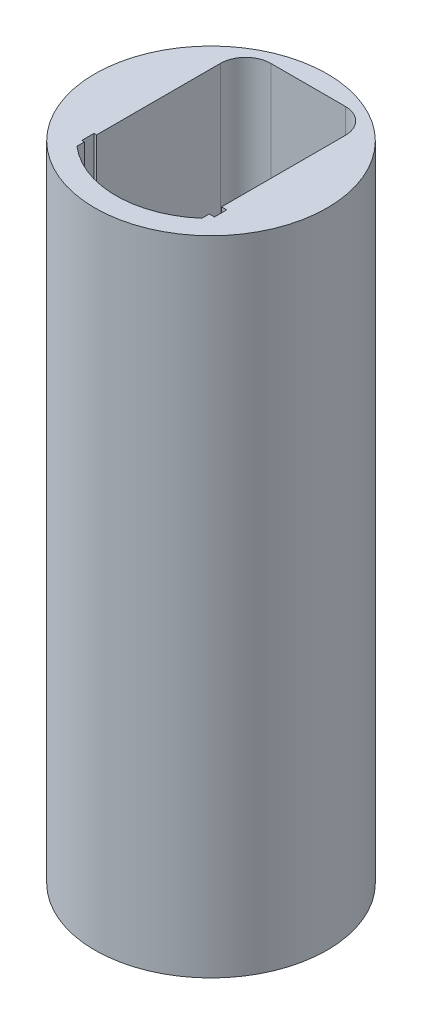
SolidWorks part; units mm, degrees
ref_plane "Front Plane" through (0, 0, 0) normal (0, 0, 1) x (1, 0, 0)
ref_plane "Top Plane" through (0, 0, 0) normal (0, 1, 0) x (1, 0, 0)
ref_plane "Right Plane" through (0, 0, 0) normal (1, 0, 0) x (0, 0, -1)
sketch "Sketch1" plane through (0, 0, 0) normal (0, 1, 0) x (1, 0, 0)
  line L0 (8.375, -6.9643) -> (9.075, -6.9643)
  line L1 (-8.725, -6.9643) -> (-8.375, -6.9643)
  line L2 (-8.725, -6.9643) -> (-8.725, -8.6143)
  line L3 (-8.725, -8.6143) -> (-8.375, -8.6143)
  line L4 (9.075, -6.9643) -> (9.075, -8.6143)
  line L6 (-8.375, -6.9643) -> (-8.375, -6.2043)
  line L12 (8.375, -6.9643) -> (8.375, -6.2043)
  line L14 (-8.375, -6.2043) -> (-8.375, 9.6457)
  line L16 (8.375, -6.2043) -> (8.375, 9.6457)
  line L19 (-5, 13.0207) -> (5, 13.0207)
  line L22 (-8.375, -8.6143) -> (-8.375, -9.6109)
  line L24 (8.375, -8.6143) -> (8.375, -9.6109)
  line L25 (8.375, -8.6143) -> (9.075, -8.6143)
  circle A0 centre (0, 0) radius 15.5912
  arc A1 (-5, 13.0207) -> (-8.375, 9.6457) centre (-5, 9.6457) ccw
  arc A2 (8.375, 9.6457) -> (5, 13.0207) centre (5, 9.6457) ccw
  arc A4 (-8.375, -9.6109) -> (8.375, -9.6109) centre (0, 0) ccw
  dimension "D5" = 16.75
  dimension "D6" = 0.76
  dimension "D1" = 17.8
  dimension "D2" = 1.65
  dimension "D3" = 15.85
  dimension "D4" = 10
  dimension "D8" = 0.35
  dimension "D9" = 0.7
extrude "Boss-Extrude1" add sketch "Sketch1" along normal blind 71
sketch "Sketch2" plane through (0, 0, 0) normal (0, -1, 0) x (1, 0, 0)
  line L1 (-8.725, 8.6143) -> (9.075, 8.6143)
  line L2 (-8.725, 8.6143) -> (-8.725, 6.9643)
  line L3 (-8.725, 6.9643) -> (9.075, 6.9643)
  line L4 (9.075, 8.6143) -> (9.075, 6.9643)
  circle A0 centre (0, 0) radius 15.5912
extrude "Boss-Extrude2" add sketch "Sketch2" along normal blind 1.25
sketch "Sketch3" plane through (0, -1.25, 0) normal (0, -1, 0) x (1, 0, 0)
  circle A0 centre (0, 0) radius 15.5912
extrude "Boss-Extrude3" add sketch "Sketch3" along normal blind 4
sketch "Sketch16" plane through (0, 0, 0) normal (0, 1, 0) x (1, 0, 0)
  line L0 (-3, -9.9011) -> (0, -9.9011)
  line L1 (0, -9.9011) -> (3, -9.9011)
  line L2 (3, -9.9011) -> (6, -9.9011)
  line L3 (-3, -9.9011) -> (-6, -9.9011)
  line L5 (-1.4599, -11.5773) -> (1.5401, -11.5773)
  line L6 (1.5401, -11.5773) -> (4.5401, -11.5773)
  circle A0 centre (0, -9.9011) radius 0.75
  circle A1 centre (3, -9.9011) radius 0.75
  circle A2 centre (-3, -9.9011) radius 0.75
  circle A3 centre (-6, -9.9011) radius 0.75
  circle A4 centre (6, -9.9011) radius 0.75
  circle A6 centre (1.5401, -11.5773) radius 0.75
  arc A9 (5.2892, -11.5989) -> (4.0065, -12.102) centre (4.5396, -11.5745) ccw
  arc A10 (-3.9429, -12.1229) -> (-5.2052, -11.6369) centre (-4.4576, -11.5773) ccw
  circle A11 centre (-1.4576, -11.5771) radius 0.75
  arc A12 (4.0065, -12.102) -> (5.2892, -11.5989) centre (0, 0) ccw
  arc A13 (-5.2052, -11.6369) -> (-3.9429, -12.1229) centre (0, 0) ccw
  dimension "D1" = 1.5
  dimension "D2" = 3
  dimension "D3" = 1.5
  dimension "D4" = 3
extrude "Cut-Extrude4" cut sketch "Sketch16" against normal blind 11.5 contours A4 | L2 A1 L1 | L1 A1 L2 | L1 A0 L0 | L0 A0 L1 | L0 A2 L3 | L3 A2 L0 | A3 | A6 | A0 | A9 A12 | A11 | A10 A13 region at (-3, 0, 9.5828) region at (-3, 0, 10.2194) region at (6, 0, 9.1723) region at (3, 0, 9.5828) region at (3, 0, 10.2194) region at (0, 0, 9.5828) region at (0, 0, 10.2194) region at (-6.7288, 0, 9.9011)
sketch "Sketch18" plane through (0, -5.25, 0) normal (0, -1, 0) x (1, 0, 0)
  circle A0 centre (0, 0) radius 15.5912
  circle A1 centre (0, 0) radius 13.0957
extrude "Boss-Extrude8" add sketch "Sketch18" along normal blind 10
fillet "Fillet3" radius 7 1 edges at (0, -5.25, -13.0957)
